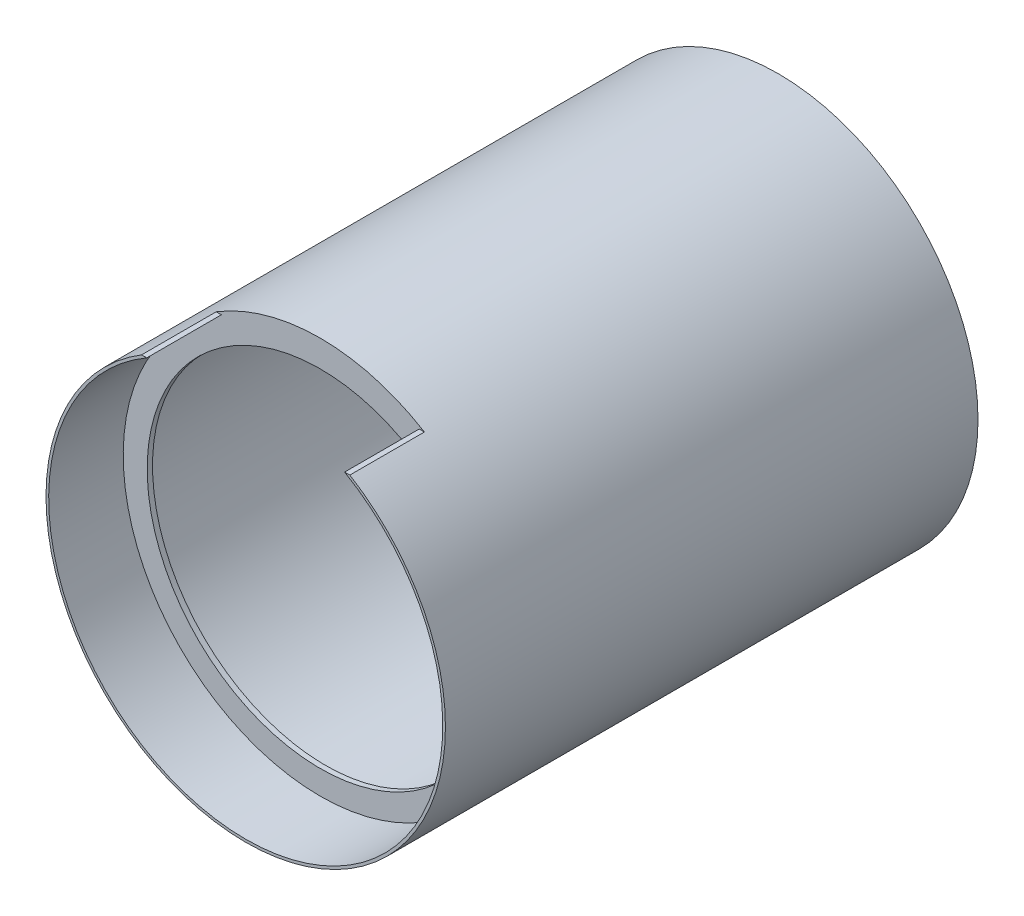
SolidWorks part; units mm, degrees
ref_plane "前视基准面" through (0, 0, 0) normal (0, 0, 1) x (1, 0, 0)
ref_plane "上视基准面" through (0, 0, 0) normal (0, 1, 0) x (1, 0, 0)
ref_plane "右视基准面" through (0, 0, 0) normal (1, 0, 0) x (0, 0, -1)
sketch "草图1" plane through (0, 0, 0) normal (0, 0, 1) x (1, 0, 0)
  circle A0 centre (0, 0) radius 75
  dimension "D1" = 150
extrude "凸台-拉伸1" add sketch "草图1" along normal blind 100 and the other way blind 100
shell "抽壳1" thickness 1 removed face at (75, 0, -100) removed face at (75, 0, 100)
ref_plane "基准面1" through (0, 0, 70) normal (0, 0, 1) x (1, 0, 0)
sketch "草图2" plane through (0, 0, 70) normal (0, 0, 1) x (1, 0, 0)
  circle A0 centre (0, 0) radius 75
  circle A1 centre (0, 0) radius 65
  dimension "D1" = 150
  dimension "D2" = 130
extrude "凸台-拉伸2" add sketch "草图2" along normal blind 2
sketch "草图3" plane through (0, 0, 100) normal (0, 0, 1) x (1, 0, 0)
  line L0 (0, 0) -> (0, 116.4423) construction
  line L1 (39.1024, 64) -> (-39.1024, 64)
  circle A0 centre (0, 0) radius 75 construction
  arc A1 (39.1024, 64) -> (-39.1024, 64) centre (0, 0) ccw
  point P7 (0, 0)
  point P10 (0, 64)
extrude "切除-拉伸1" cut sketch "草图3" against normal up to surface (28 mm away) up to face at (65, 0, 72)
